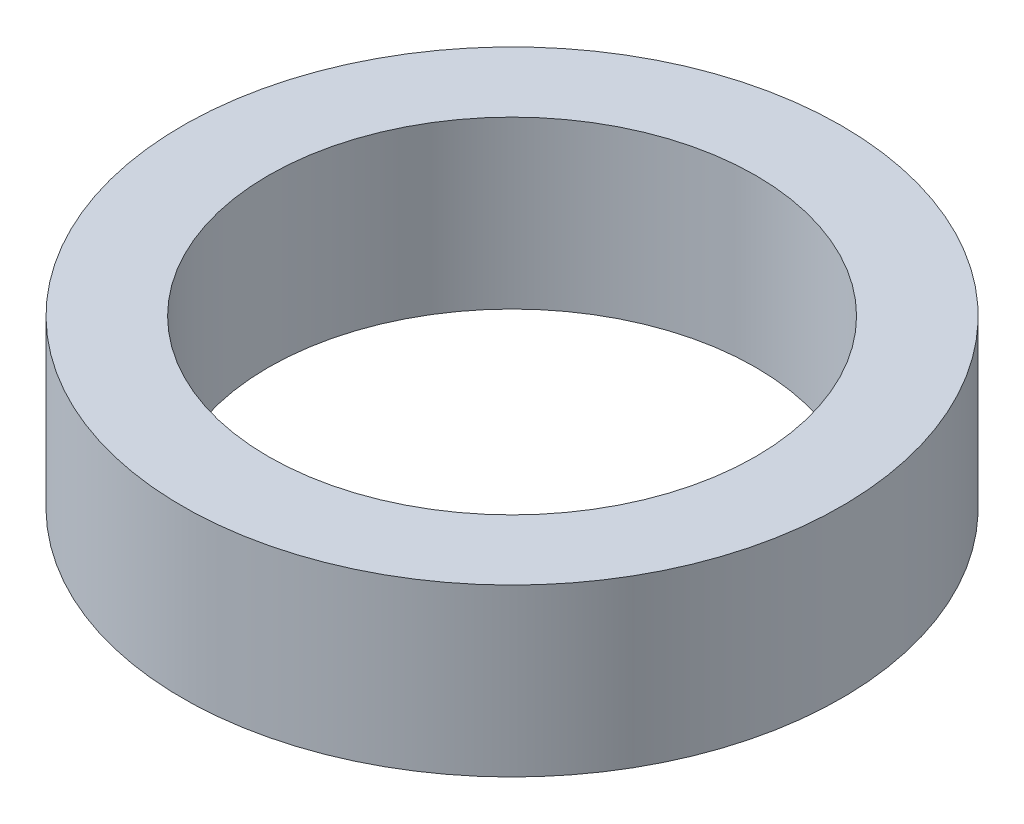
SolidWorks part; units mm, degrees
ref_plane "Front Plane" through (0, 0, 0) normal (0, 0, 1) x (1, 0, 0)
ref_plane "Top Plane" through (0, 0, 0) normal (0, 1, 0) x (1, 0, 0)
ref_plane "Right Plane" through (0, 0, 0) normal (1, 0, 0) x (0, 0, -1)
sketch "Sketch1" plane through (0, 0, 0) normal (0, 1, 0) x (1, 0, 0)
  circle A0 centre (0, 0) radius 57.5
  dimension "FLANGE_OD" = 115
extrude "Boss-Extrude1" add sketch "Sketch1" along normal blind 29
sketch "Sketch2" plane through (0, 0, 0) normal (0, 1, 0) x (1, 0, 0)
  circle A0 centre (0, 0) radius 42.5
  dimension "BORE_D" = 85
extrude "Cut-Extrude1" cut sketch "Sketch2" along normal through all
sketch "Sketch3" plane through (0, 29, 0) normal (0, 1, 0) x (1, 0, 0)
  circle A0 centre (0, 0) radius 24.3344 construction
  circle A1 centre (-24.3344, 0) radius 2.3202
  dimension "BOLT_D" = 4.6405
  dimension "BOLT_PCD" = 48.6687
extrude "Cut-Extrude2" cut sketch "Sketch3" against normal blind 20.0341 rebuild error yes
pattern_circular "CirPattern1" count 3 over 360 rebuild error yes
